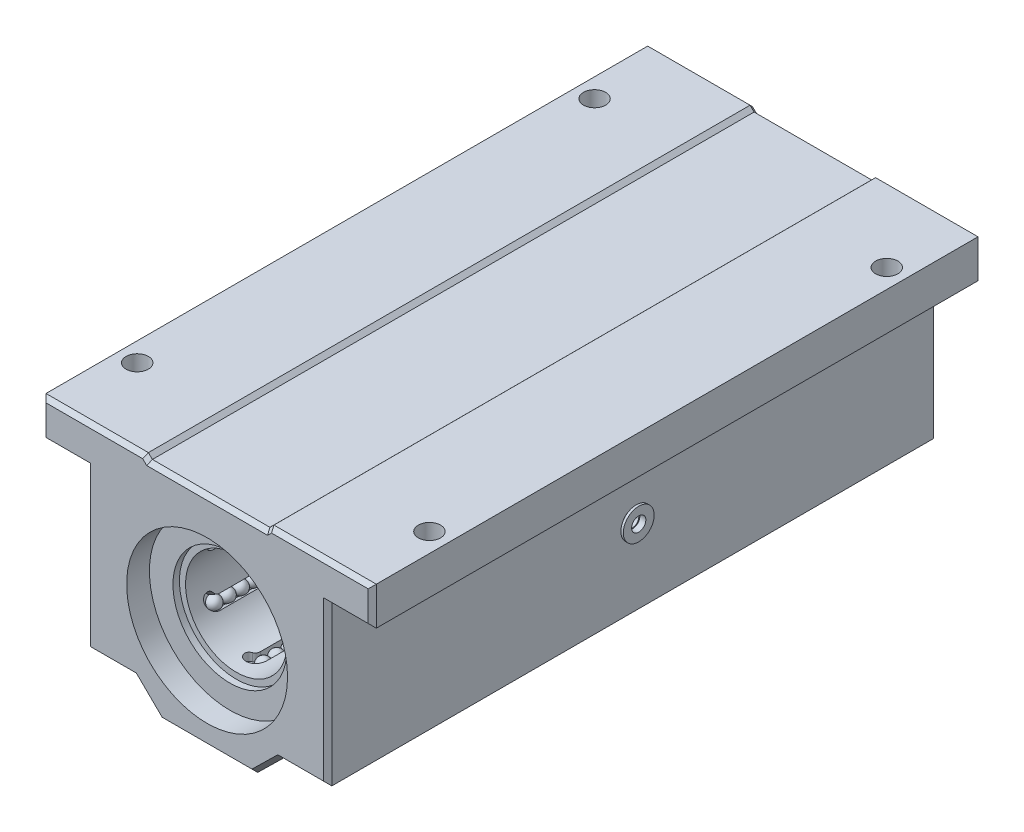
SolidWorks part; units mm, degrees
ref_plane "Front" through (0, 0, 0) normal (0, 0, 1) x (1, 0, 0)
ref_plane "Top" through (0, 0, 0) normal (0, 1, 0) x (1, 0, 0)
ref_plane "Right" through (0, 0, 0) normal (1, 0, 0) x (0, 0, -1)
sketch "Sketch1" plane through (0, 0, 0) normal (0, 0, 1) x (1, 0, 0)
  line L0 (0, 27.7812) -> (0, -27.7812) construction
  line L1 (-41.275, 27.7813) -> (-15.6845, 27.7812)
  line L2 (-41.275, 27.7813) -> (-41.275, 18.2563)
  line L3 (-41.275, 18.2563) -> (-30.1625, 18.2563)
  line L4 (-30.1625, 18.2563) -> (-30.1625, -21.4439)
  line L5 (-30.1625, -21.4439) -> (-18.0975, -21.4439)
  line L6 (-18.0975, -21.4439) -> (-11.6385, -27.7813)
  line L7 (-11.6385, -27.7813) -> (11.6385, -27.7812)
  line L8 (-15.6845, 27.7812) -> (-14.6836, 26.7935)
  line L9 (-14.6836, 26.7935) -> (14.6836, 26.7935)
  line L10 (15.6845, 27.7813) -> (14.6836, 26.7935)
  line L11 (18.0975, -21.4439) -> (11.6385, -27.7812)
  line L12 (30.1625, -21.4439) -> (18.0975, -21.4439)
  line L13 (30.1625, 18.2563) -> (30.1625, -21.4439)
  line L14 (41.275, 18.2563) -> (30.1625, 18.2563)
  line L15 (41.275, 27.7813) -> (41.275, 18.2563)
  line L16 (41.275, 27.7813) -> (15.6845, 27.7813)
  point P12 (0, 26.7935)
  dimension "MMC F " = 55.5625
  dimension "MMC H " = 9.525
  dimension "Supplier M " = 60.325
  dimension "MMC D " = 82.55
  dimension "Supplier G " = 49.2252
  dimension "D6" = 9.0488
  dimension "D7" = 12.065
  dimension "D8" = 29.3672
  dimension "D9" = 0.9878
  dimension "D10" = 25.5905
extrude "Extrude1" add sketch "Sketch1" along normal mid plane 152.4
sketch "Sketch2" plane through (0, 0, 76.2) normal (0, 0, 1) x (1, 0, 0)
  line L0 (41.275, 27.7813) -> (15.6845, 27.7813) construction
  line L1 (0, -50) -> (0, 50) construction
  line L2 (0, -27.7813) -> (0, -22.4896) construction
  line L3 (-11.6385, -27.7813) -> (11.6385, -27.7812) construction
  circle A0 centre (0, -2.3812) radius 20.1083
  dimension "D2" = 40.2167
  dimension "MMC G " = 30.1625
extrude "Cut-Extrude1" cut sketch "Sketch2" against normal blind 5.6896
sketch "Sketch3" plane through (0, 0, 70.5104) normal (0, 0, 1) x (1, 0, 0)
  line L0 (0, 0) -> (0, 23.0187) construction
  line L1 (0, -50) -> (0, 50) construction
  line L2 (0, 0) -> (0, 41.1582) construction
  line L3 (0, 0) -> (0, -22.4896) construction
  line L4 (0, 0) -> (-5.1943, -19.3856) construction
  line L5 (0, 0) -> (-4.2819, -22.0284) construction
  line L6 (-3.3985, -17.4836) -> (-4.2819, -22.0284)
  line L7 (0, 0) -> (4.2819, -22.0284) construction
  line L8 (0, 0) -> (5.1943, -19.3856) construction
  line L9 (3.3985, -17.4836) -> (4.2819, -22.0284)
  arc A0 (0, 15.234) -> (-9.7394, -17.7727) centre (0.5086, -2.8564) ccw
  circle A1 centre (0, -2.3812) radius 17.78 construction
  arc A2 (4.2819, -22.0284) -> (-4.2819, -22.0284) centre (0, -2.3812) ccw
  circle A3 centre (0, -2.3812) radius 20.1083 construction
  circle A4 centre (0, -2.3812) radius 20.1083 construction
  circle A5 centre (5.1943, -19.3856) radius 0.5027
  arc A6 (-9.7394, -17.7727) -> (-5.3593, -16.8409) centre (-7.9915, -15.2286) ccw
  arc A7 (-5.3593, -16.8409) -> (-3.3985, -17.4836) centre (-2.8466, -12.4869) ccw
  arc A8 (5.3593, -16.8409) -> (3.3985, -17.4836) centre (2.8466, -12.4869) cw
  arc A9 (9.7394, -17.7727) -> (5.3593, -16.8409) centre (7.9915, -15.2286) cw
  circle A10 centre (-5.1943, -19.3856) radius 0.5027
  arc A11 (0, 15.234) -> (9.7394, -17.7727) centre (-0.5086, -2.8564) cw
  dimension "D1" = 18.0975
  dimension "D4" = 3.0868
  dimension "D6" = 12.4869
  dimension "D7" = 2.8466
  dimension "D8" = 35.56
  dimension "D9" = 1.0054
  dimension "D10" = 15
  dimension "D12" = 5.0271
  dimension "D2" = 2.8564
  dimension "D3" = 0.5086
  dimension "D5" = 7.9915
  dimension "D11" = 11
sketch "Sketch4" plane through (0, 0, 70.5104) normal (0, 0, 1) x (1, 0, 0)
  circle A0 centre (0, -2.3812) radius 14.2266
  circle A2 centre (0, -2.3812) radius 20.1083 construction
  dimension "D1" = 28.4533
extrude "Cut-Extrude2" cut sketch "Sketch4" against normal blind 1.6256
mirror "Mirror1" about plane through (0, 0, 0) normal (0, 0, 1) of "Cut-Extrude2", "Cut-Extrude1"
sketch "Sketch5" plane through (0, 0, 68.8848) normal (0, 0, 1) x (1, 0, 0)
  circle A0 centre (0, -2.3812) radius 12.7
  circle A1 centre (0, -2.3812) radius 14.2266 construction
  dimension "ID " = 25.4
extrude "Cut-Extrude3" cut sketch "Sketch5" against normal through all
sketch "Sketch6" plane through (0, 0, 0) normal (1, 0, 0) x (0, 0, -1)
  line L0 (-15.6464, 15.2576) -> (-15.6464, 10.3188)
  line L2 (-76.2, 27.7813) -> (76.2, 27.7813) construction
  line L5 (-68.8848, 10.3188) -> (-68.8848, -15.0812) construction
  line L6 (-76.2, -21.4439) -> (-76.2, 18.2563) construction
  line L7 (-68.8848, -2.3812) -> (68.8848, -2.3812) construction
  line L8 (-68.8848, 10.3188) -> (-15.6464, 10.3188) construction
  line L9 (68.8848, -15.0812) -> (68.8848, 10.3188) construction
  line L12 (-15.6464, 15.2576) -> (15.6464, 15.2576)
  line L13 (0, 50) -> (0, -50) construction
  line L14 (0, 0) -> (0, 27.7813) construction
  line L15 (-15.6464, 10.3188) -> (15.6464, 10.3188)
  line L16 (15.6464, 15.2576) -> (15.6464, 10.3188)
  point P5 (0, 10.3188)
  point P16 (0, 15.2576)
  dimension "D1" = 60.5536
  dimension "D2" = 4.9389
revolve "Cut-Revolve1" cut sketch "Sketch6" angle 360 about L7
sketch "Sketch7" plane through (0, 0, 0) normal (1, 0, 0) x (0, 0, -1)
  line L0 (-15.6464, 15.2576) -> (-15.6464, 10.0648)
  line L1 (-15.6464, 10.0648) -> (15.6464, 10.0648)
  line L2 (15.6464, 15.2576) -> (-15.6464, 15.2576)
  line L3 (15.6464, 10.0648) -> (15.6464, 15.2576)
  line L4 (-15.6464, -15.0812) -> (-15.6464, 10.3188) construction
  line L13 (-68.8848, -2.3812) -> (0, -2.3812) construction
  line L14 (-68.8848, 11.8454) -> (-68.8848, -16.6079) construction
  line L15 (0, 50) -> (0, -50) construction
  dimension "D1" = 12.446
revolve "Revolve1" add sketch "Sketch7" angle 360 about L13
ref_plane "Plane1" through (0, -2.3812, 0) normal (0, 1, 0) x (-1, 0, 0)
sketch "Sketch8" plane through (0, -2.3812, 0) normal (0, 1, 0) x (-1, 0, 0)
  line L0 (0, 68.8848) -> (0, 15.6756) construction
  line L1 (14.2266, 68.8848) -> (-14.2266, 68.8848) construction
  line L2 (1.3875, 19.1853) -> (1.3875, 21.9602) construction
  line L3 (0, 42.2802) -> (-41.275, 42.2802) construction
  line L4 (-41.275, 76.2) -> (-41.275, -76.2) construction
  line L5 (1.3875, 61.5158) -> (1.3875, 23.0446)
  line L6 (-1.3875, 21.9602) -> (1.3875, 21.9602) construction
  line L7 (1.3875, -65.3752) -> (1.3875, -62.6002) construction
  line L8 (-1.3875, -62.6002) -> (1.3875, -62.6002) construction
  line L9 (-1.3875, -21.9602) -> (1.3875, -21.9602) construction
  line L10 (0, -42.2802) -> (-41.275, -42.2802) construction
  line L11 (1.3875, -19.1853) -> (1.3875, -21.9602) construction
  line L12 (-1.3875, 21.9602) -> (-1.3875, 62.6002)
  line L13 (0, -68.8848) -> (0, -15.6756) construction
  line L14 (-1.3875, 62.6002) -> (1.3875, 62.6002) construction
  line L15 (1.3875, 65.3752) -> (1.3875, 62.6002) construction
  line L16 (0, 0) -> (98.9742, 0) construction
  line L17 (50, 0) -> (-50, 0) construction
  line L18 (-1.3875, -21.9602) -> (-1.3875, -62.6002)
  line L19 (1.3875, -61.5158) -> (1.3875, -23.0446)
  line L20 (-14.6836, 76.2) -> (14.6836, 76.2) construction
  arc A0 (-1.3875, 62.6002) -> (1.3875, 65.3752) centre (1.3875, 62.6002) cw
  arc A1 (2.1101, 62.8033) -> (1.3875, 65.3752) centre (1.3875, 63.9877) ccw
  arc A2 (2.1101, 62.8033) -> (1.3875, 61.5158) centre (2.8956, 61.5158) ccw
  arc A3 (2.1101, 21.7572) -> (1.3875, 23.0446) centre (2.8956, 23.0446) cw
  arc A4 (2.1101, 21.7572) -> (1.3875, 19.1853) centre (1.3875, 20.5727) cw
  arc A5 (-1.3875, 21.9602) -> (1.3875, 19.1853) centre (1.3875, 21.9602) ccw
  arc A6 (-1.3875, -21.9602) -> (1.3875, -19.1853) centre (1.3875, -21.9602) cw
  arc A7 (2.1101, -21.7572) -> (1.3875, -19.1853) centre (1.3875, -20.5727) ccw
  arc A8 (2.1101, -21.7572) -> (1.3875, -23.0446) centre (2.8956, -23.0446) ccw
  arc A9 (2.1101, -62.8033) -> (1.3875, -61.5158) centre (2.8956, -61.5158) cw
  arc A10 (2.1101, -62.8033) -> (1.3875, -65.3752) centre (1.3875, -63.9877) cw
  arc A11 (-1.3875, -62.6002) -> (1.3875, -65.3752) centre (1.3875, -62.6002) ccw
  point P8 (-1.3875, 42.2802)
  point P10 (1.3875, 42.2802)
  point P28 (-1.3875, 42.2802)
  point P30 (1.3875, 42.2802)
  point P47 (1.3875, -42.2802)
  point P48 (-1.3875, -42.2802)
  dimension "D3" = 1.5081
  dimension "D4" = 1.3875
  dimension "D5" = 12.2123
  dimension "D1" = 2.775
  dimension "D2" = 20.32
extrude "Cut-Extrude4" cut sketch "Sketch8" against normal offset from surface (14.6098 mm away) 1.9756
pattern_circular "CirPattern1" count 6 over 360 about axis through (0, -2.3812, 0) along (0, 0, 1) of "Cut-Extrude4"
sketch "Sketch9" plane through (0, 0, 0) normal (1, 0, 0) x (0, 0, -1)
  line L0 (-15.6464, -2.3812) -> (-68.8848, -2.3812) construction
  line L2 (-68.8848, 11.8454) -> (-68.8848, -16.6079) construction
  line L3 (-42.2656, -2.3812) -> (-42.2656, 27.7812) construction
  line L4 (-15.6464, 10.0648) -> (-15.6464, -14.8272) construction
  line L5 (-76.2, 27.7813) -> (76.2, 27.7813) construction
ref_plane "Plane2" through (0, 0, 42.2656) normal (0, 0, 1) x (1, 0, 0)
sketch "Sketch10" plane through (0, 0, 42.2656) normal (0, 0, 1) x (1, 0, 0)
  line L0 (-1.3875, -15.0052) -> (-1.3875, -16.9911) construction
  line L1 (1.3875, -15.0052) -> (1.3875, -16.9911) construction
  line L2 (-1.3875, -16.9911) -> (1.3875, -16.9911) construction
  line L3 (-1.6388, -16.7201) -> (1.6388, -16.7201)
  circle A0 centre (0, -2.3812) radius 12.7 construction
  circle A2 centre (0, -2.3812) radius 12.7 construction
  arc A3 (1.6388, -16.7201) -> (-1.6388, -16.7201) centre (0, -16.7201) ccw
  dimension "D1" = 0.2514
  dimension "D2" = 0.2514
revolve "Revolve2" add sketch "Sketch10" angle 360 about L3
pattern_linear "LPattern1" count 7 spacing 3.302 along (0, 0, 1) of "Revolve2"
mirror "Mirror2" about plane through (0, 0, 42.2656) normal (0, 0, 1) of "LPattern1", "Revolve2"
pattern_circular "CirPattern2" count 6 over 360 about axis through (0, -2.3812, 0) along (0, 0, 1) of "LPattern1", "Revolve2", "Mirror2"
mirror "Mirror3" about plane through (0, 0, 0) normal (0, 0, 1) of "CirPattern2", "Mirror2", "LPattern1", "Revolve2"
chamfer "Chamfer1" distance 1.016 angle 45 32 edges at (30.1625, -1.5938, -76.2) (24.13, -21.4439, -76.2) (14.868, -24.6126, -76.2) (0, -27.7812, -76.2) (-14.868, -24.6126, -76.2) (-24.13, -21.4439, -76.2) (-30.1625, -1.5938, -76.2) (-35.7187, 18.2563, -76.2) (-41.275, 23.0188, -76.2) (-28.4797, 27.7812, -76.2) (-15.184, 27.2874, -76.2) (0, 26.7935, -76.2) (15.184, 27.2874, -76.2) (28.4797, 27.7813, -76.2) (41.275, 23.0188, -76.2) (35.7187, 18.2563, -76.2) (15.184, 27.2874, 76.2) (0, 26.7935, 76.2) (-15.184, 27.2874, 76.2) (-28.4797, 27.7812, 76.2) (-41.275, 23.0188, 76.2) (-35.7187, 18.2563, 76.2) (-30.1625, -1.5938, 76.2) (-24.13, -21.4439, 76.2) (-14.868, -24.6126, 76.2) (0, -27.7812, 76.2) (14.868, -24.6126, 76.2) (24.13, -21.4439, 76.2) (30.1625, -1.5938, 76.2) (35.7187, 18.2563, 76.2) (41.275, 23.0188, 76.2) (28.4797, 27.7813, 76.2)
sketch "Sketch11" plane through (30.1625, 0, 0) normal (1, 0, 0) x (0, 0, -1)
  line L0 (-75.184, -1.5938) -> (75.184, -1.5938) construction
  line L1 (-75.184, 18.2563) -> (-75.184, -21.4439) construction
  line L2 (75.184, -21.4439) -> (75.184, 18.2563) construction
  line L3 (0, -1.5938) -> (0, 27.7813) construction
  line L4 (-75.184, 27.7813) -> (75.184, 27.7813) construction
  circle A0 centre (0, -1.5938) radius 1.524
  dimension "D1" = 3.048
extrude "Cut-Extrude5" cut sketch "Sketch11" against normal blind 2.0108
sketch "Sketch12" plane through (0, 0, 0) normal (0, 0, 1) x (1, 0, 0)
  line L0 (30.1625, -1.5938) -> (102.8363, -1.5938) construction
  line L1 (30.1625, -3.1178) -> (30.1625, -0.0698) construction
  line L2 (30.1625, 0.1841) -> (30.1625, 1.0478)
  line L3 (30.1625, 18.2563) -> (30.1625, -21.4439) construction
  line L4 (30.1625, 1.0478) -> (31.0674, 1.0478)
  line L5 (31.0674, 1.0478) -> (31.0674, 2.267)
  line L6 (31.0674, 2.267) -> (31.6706, 2.267)
  line L7 (31.6706, 2.267) -> (31.6706, 0.1841)
  line L8 (31.6706, 0.1841) -> (30.1625, 0.1841)
  dimension "D1" = 3.556
  dimension "D2" = 7.7216
  dimension "D3" = 5.2832
  dimension "D4" = 0.6032
  dimension "D5" = 1.5081
revolve "Revolve3" add sketch "Sketch12" angle 360 about L0
sketch "Sketch13" plane through (0, 27.7812, 0) normal (0, 1, 0) x (1, 0, 0)
  line L0 (36.5125, 0) -> (-36.5125, 0) construction
  line L1 (-36.5125, 57.15) -> (36.5125, 57.15) construction
  line L2 (-36.5125, 57.15) -> (-36.5125, -57.15) construction
  line L3 (-36.5125, -57.15) -> (36.5125, -57.15) construction
  line L4 (36.5125, 57.15) -> (36.5125, -57.15) construction
  line L6 (0, 57.15) -> (0, -57.15) construction
  circle A0 centre (-36.5125, 57.15) radius 2.7781
  circle A1 centre (36.5125, 57.15) radius 2.7781
  circle A2 centre (36.5125, -57.15) radius 2.7781
  circle A3 centre (-36.5125, -57.15) radius 2.7781
  dimension "MMC L " = 5.5562
  dimension "MMC K " = 114.3
  dimension "MMC J " = 73.025
extrude "Cut-Extrude6" cut sketch "Sketch13" against normal up to surface (9.525 mm away) up to face at (35.7187, 18.2563, 0)
equation "\"D9@Sketch1\" = \"MMC F @Sketch1\" * .017777777778"
equation "\"D7@Sketch1\" = \"Supplier M @Sketch1\" * .2"
equation "\"D6@Sketch1\" = \"Supplier M @Sketch1\" * .15"
equation "\"D10@Sketch1\" = \"MMC D @Sketch1\" * .31"
equation "\"D8@Sketch1\" = \"MMC D @Sketch1\" * .35575"
equation "\"D2@Sketch2\" = \"Supplier M @Sketch1\" * .6666666667"
equation "\"D1@Cut-Extrude1\" = \"MMC B @Extrude1\" * .0373333333333333"
equation "\"D3@Sketch3\" = \"Supplier M @Sketch1\" * .0084304733"
equation "\"D5@Sketch3\" = \"Supplier M @Sketch1\" * .13247389"
equation "\"D7@Sketch3\" = \"Supplier M @Sketch1\" * .0471872433"
equation "\"D4@Sketch3\" = \"Supplier M @Sketch1\" * .0511690833"
equation "\"D12@Sketch3\" = \"Supplier M @Sketch1\" * .083333333333"
equation "\"D9@Sketch3\" = \"Supplier M @Sketch1\" * .0166666667"
equation "\"D1@Sketch3\" = \"Supplier M @Sketch1\" * .3"
equation "\"D2@Sketch3\" = \"MMC F @Sketch1\" * .0514082169"
equation "\"D6@Sketch3\" = \"MMC F @Sketch1\" * .2247355733"
equation "\"D8@Sketch3\" = \"MMC F @Sketch1\" * .64"
equation "\"D1@Sketch4\" = \"Supplier M @Sketch1\" * .4716666667"
equation "\"D1@Cut-Extrude2\" = \"MMC B @Extrude1\" * .0106666667"
equation "\"D1@Sketch6\" = \"MMC B @Extrude1\" * .3973333333"
equation "\"D2@Sketch6\" = \"MMC F @Sketch1\" * .088888888889"
equation "\"D1@Sketch7\" = \"ID @Sketch5\" * .49"
equation "\"D1@Cut-Extrude4\" = \"MMC F @Sketch1\" * .0355555556"
equation "\"D2@Sketch8\" = \"MMC B @Extrude1\" * .13333333333"
equation "\"D5@Sketch8\" = \"MMC B @Extrude1\" * .080133333"
equation "\"D3@Sketch8\" = \"Supplier M @Sketch1\" * .025"
equation "\"D4@Sketch8\" = \"Supplier M @Sketch1\" * .023"
equation "\"D1@Sketch8\" = \"Supplier M @Sketch1\" * .046"
equation "\"D1@Sketch10\" = \"Supplier M @Sketch1\" * .0041666667"
equation "\"D2@Sketch10\" = \"Supplier M @Sketch1\" * .0041666667"
equation "\"D1@Chamfer1\" = \"MMC B @Extrude1\" * .00666666667"
equation "\"D1@Sketch11\" = \"MMC B @Extrude1\" * .02"
equation "\"D1@Cut-Extrude5\" = \"Supplier M @Sketch1\" * .0333333333"
equation "\"D5@Sketch12\" = \"Supplier M @Sketch1\" * .025"
equation "\"D4@Sketch12\" = \"Supplier M @Sketch1\" * .01"
equation "\"D2@Sketch12\" = \"MMC B @Extrude1\" * .0506666667"
equation "\"D3@Sketch12\" = \"MMC B @Extrude1\" * .0346666667"
equation "\"D1@Sketch12\" = \"MMC B @Extrude1\" * .02333333333"
